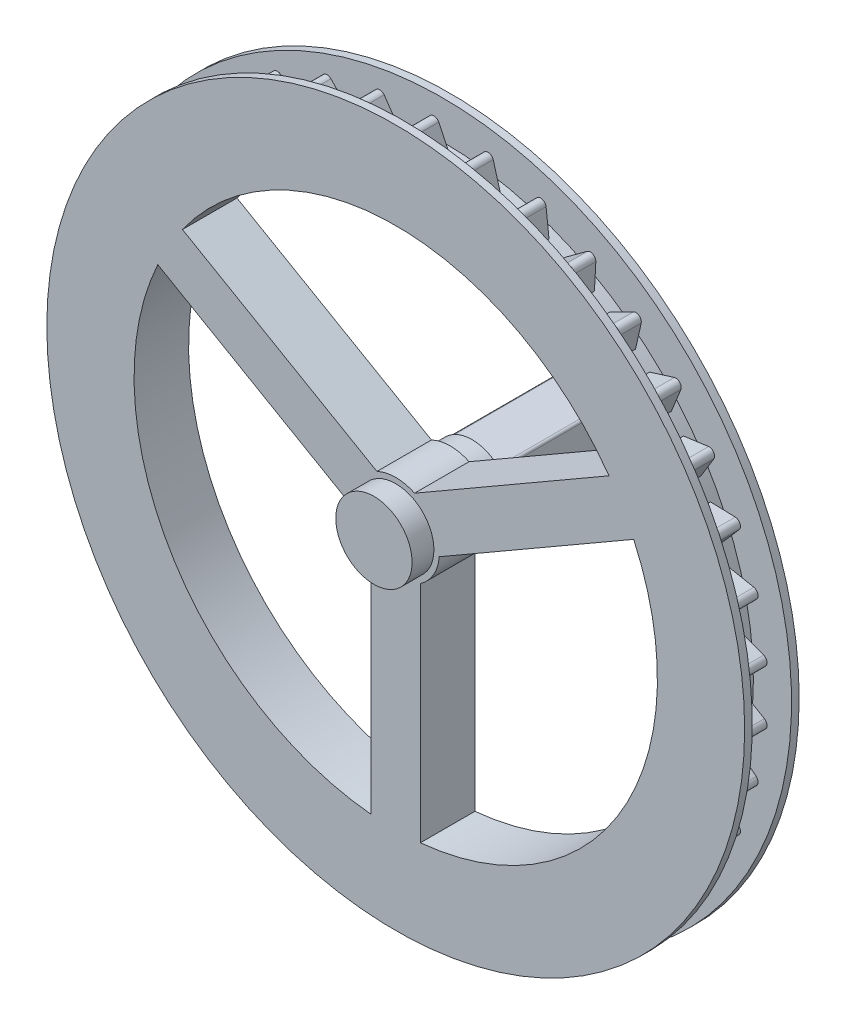
SolidWorks part; units mm, degrees
ref_plane "Front" through (0, 0, 0) normal (0, 0, 1) x (1, 0, 0)
ref_plane "Top" through (0, 0, 0) normal (0, 1, 0) x (1, 0, 0)
ref_plane "Right" through (0, 0, 0) normal (1, 0, 0) x (0, 0, -1)
sketch "Sketch1" plane through (0, 0, 0) normal (0, 0, 1) x (1, 0, 0)
  circle A0 centre (0, 0) radius 40
  dimension "D1" = 80
extrude "Boss-Extrude1" add sketch "Sketch1" along normal blind 5
sketch "Sketch2" plane through (0, 0, 5) normal (0, 0, 1) x (1, 0, 0)
  line L0 (0, 0) -> (0, 40) construction
  line L2 (-2.1584, 4.5101) -> (-24.4518, 17.3813)
  line L4 (2.1584, 4.5101) -> (24.4518, 17.3813)
  line L5 (4.9851, -0.3858) -> (27.2785, 12.4853)
  line L6 (2.8267, -4.1243) -> (2.8267, -29.8665)
  line L7 (0, 0) -> (34.641, -20) construction
  line L8 (-2.8267, -4.1243) -> (-2.8267, -29.8665)
  line L9 (-4.9851, -0.3858) -> (-27.2785, 12.4853)
  line L10 (0, 0) -> (-34.641, -20) construction
  arc A0 (2.1584, 4.5101) -> (-2.1584, 4.5101) centre (0, 0) ccw
  circle A1 centre (0, 0) radius 40 construction
  arc A2 (24.4518, 17.3813) -> (-24.4518, 17.3813) centre (0, 0) ccw
  arc A3 (2.8267, -4.1243) -> (4.9851, -0.3858) centre (0, 0) ccw
  arc A4 (2.8267, -29.8665) -> (27.2785, 12.4853) centre (0, 0) ccw
  arc A5 (-4.9851, -0.3858) -> (-2.8267, -4.1243) centre (0, 0) ccw
  arc A6 (-27.2785, 12.4853) -> (-2.8267, -29.8665) centre (0, 0) ccw
  point P23 (0, 0)
  dimension "D1" = 10
  dimension "D2" = 60
  dimension "D3" = 60
  dimension "D4" = 3
extrude "Cut-Extrude1" cut sketch "Sketch2" against normal blind 5
scale "Scale1" scale about centroid uniform scaling yes scale factor 0.8
sketch "Sketch4" plane through (0, 0, 4.5) normal (0, 0, 1) x (1, 0, 0)
  line L0 (-2.2614, -23.8932) -> (-2.2614, -3.2994) construction
  line L1 (2.2614, -3.2994) -> (2.2614, -23.8932) construction
  line L2 (21.8228, 9.9882) -> (3.9881, -0.3087) construction
  line L3 (-19.5615, 13.905) -> (-1.7267, 3.6081) construction
  line L4 (1.7267, 3.6081) -> (19.5615, 13.905) construction
  line L5 (-2.2614, -23.8932) -> (-2.2614, -3.2994)
  line L6 (2.2614, -3.2994) -> (2.2614, -23.8932)
  line L7 (21.8228, 9.9882) -> (3.9881, -0.3087)
  line L8 (-19.5615, 13.905) -> (-1.7267, 3.6081)
  line L9 (1.7267, 3.6081) -> (19.5615, 13.905)
  circle A0 centre (0, 0) radius 32 construction
  arc A1 (2.2614, -23.8932) -> (21.8228, 9.9882) centre (0, 0) ccw construction
  arc A2 (-21.8228, 9.9882) -> (-2.2614, -23.8932) centre (0, 0) ccw construction
  arc A3 (2.2614, -3.2994) -> (3.9881, -0.3087) centre (0, 0) ccw construction
  arc A4 (1.7267, 3.6081) -> (-1.7267, 3.6081) centre (0, 0) ccw construction
  arc A5 (19.5615, 13.905) -> (-19.5615, 13.905) centre (0, 0) ccw construction
  circle A6 centre (0, 0) radius 32
  arc A7 (2.2614, -23.8932) -> (21.8228, 9.9882) centre (0, 0) ccw
  arc A8 (-21.8228, 9.9882) -> (-2.2614, -23.8932) centre (0, 0) ccw
  arc A9 (2.2614, -3.2994) -> (3.9881, -0.3087) centre (0, 0) ccw
  arc A10 (1.7267, 3.6081) -> (-1.7267, 3.6081) centre (0, 0) ccw
  arc A11 (19.5615, 13.905) -> (-19.5615, 13.905) centre (0, 0) ccw
  arc M1 (-3.9881, -0.3087) -> (-2.2614, -3.2994) centre (0, 0) ccw
  line M2 (-2.2614, -3.2994) -> (-2.2614, -23.8932)
  arc M3 (-2.2614, -23.8932) -> (-21.8228, 9.9882) centre (0, 0) cw
  line M4 (-21.8228, 9.9882) -> (-3.9881, -0.3087)
  arc M5 (2.2614, -3.2994) -> (3.9881, -0.3087) centre (0, 0) ccw
  line M6 (3.9881, -0.3087) -> (21.8228, 9.9882)
  arc M7 (21.8228, 9.9882) -> (2.2614, -23.8932) centre (0, 0) cw
  line M8 (2.2614, -23.8932) -> (2.2614, -3.2994)
  arc M10 (1.7267, 3.6081) -> (-1.7267, 3.6081) centre (0, 0) ccw
  line M11 (-1.7267, 3.6081) -> (-19.5615, 13.905)
  arc M12 (-19.5615, 13.905) -> (19.5615, 13.905) centre (0, 0) cw
  line M13 (19.5615, 13.905) -> (1.7267, 3.6081)
  circle M14 centre (0, 0) radius 32
extrude "Boss-Extrude2" add sketch "Sketch4" along normal blind 1 contours M14 M13 M10 M11 M12 M8 M5 M6 M7 M4 M1 M2 M3 region at (0, 0, 4.5)
sketch "Sketch7" plane through (0, 0, 0.5) normal (0, 0, -1) x (-1, 0, 0)
  circle A0 centre (0, 0) radius 3.5
  dimension "D1" = 7
extrude "Boss-Extrude3" add sketch "Sketch7" along normal blind 2
ref_plane "Plane1" through (0, 0, 0) normal (0, 0, 1) x (1, 0, 0)
ref_plane "Plane2" through (0, 0, 3) normal (0, 0, 1) x (1, 0, 0)
mirror "Mirror1" about plane through (0, 0, 3) normal (0, 0, 1) of "Boss-Extrude3"
sketch "Sketch9" plane through (0, 0, -1.5) normal (0, 0, -1) x (-1, 0, 0)
  line L0 (0, 0) -> (0, -11.4926) construction
  line L1 (-2.2614, -3.2994) -> (-2.2614, -23.8932) construction
  line L2 (0, 0) -> (-15.6668, 0) construction
  line L3 (2.45, -2.45) -> (-2.45, -2.45)
  line L4 (2.45, -2.45) -> (2.45, 2.45)
  line L5 (2.45, 2.45) -> (-2.45, 2.45)
  line L6 (-2.45, -2.45) -> (-2.45, 2.45)
  point P10 (0, -2.45)
  point P11 (-2.45, 0)
  dimension "D1" = 4.9
extrude "Boss-Extrude4" add sketch "Sketch9" along normal blind 10
fillet "Fillet1" radius 0.2 8 edges at (-2.45, 0, -11.5) (0, 2.45, -11.5) (2.45, 0, -11.5) (0, -2.45, -11.5) (2.45, -2.45, -6.5) (-2.45, -2.45, -6.5) (2.45, 2.45, -6.5) (-2.45, 2.45, -6.5)
ref_plane "Plane3" through (0, 0, 0.5) normal (0, 0, -1) x (-1, 0, 0)
ref_plane "Plane4" through (0, 0, 3) normal (0, 0, -1) x (-1, 0, 0)
sketch "Sketch10" plane through (0, 0, 3) normal (0, 0, -1) x (-1, 0, 0)
  circle A0 centre (0, 0) radius 32 construction
  circle A1 centre (0, 0) radius 32
  circle A2 centre (0, 0) radius 28.5
  dimension "D1" = 57
extrude "Cut-Extrude2" cut sketch "Sketch10" against normal blind 1.8 and the other way blind 1.8
sketch "Sketch11" plane through (0, 0, 3) normal (0, 0, -1) x (-1, 0, 0)
  line L0 (0, 0) -> (0, 28.5) construction
  line L2 (0, 28.5) -> (0, 33.0418) construction
  circle A0 centre (0, 0) radius 28.5 construction
  arc A1 (2.8558, 28.3566) -> (-2.8558, 28.3566) centre (0, 0) ccw
  arc A2 (8.5055, 27.2012) -> (2.9108, 28.351) centre (0, 0) ccw
  arc A3 (13.8069, 24.9323) -> (8.5582, 27.1847) centre (0, 0) ccw
  arc A4 (18.5431, 21.6426) -> (13.8553, 24.9055) centre (0, 0) ccw
  arc A5 (22.5202, 17.4669) -> (18.5851, 21.6066) centre (0, 0) ccw
  arc A6 (25.5753, 12.576) -> (22.554, 17.4232) centre (0, 0) ccw
  arc A7 (27.5833, 7.1703) -> (25.5996, 12.5264) centre (0, 0) ccw
  arc A8 (28.462, 1.4711) -> (27.5971, 7.1169) centre (0, 0) ccw
  arc A9 (28.1755, -4.2884) -> (28.4648, 1.4159) centre (0, 0) ccw
  arc A10 (26.7355, -9.8723) -> (28.1672, -4.343) centre (0, 0) ccw
  arc A11 (24.201, -15.052) -> (26.7163, -9.9241) centre (0, 0) ccw
  arc A12 (20.6756, -19.6155) -> (24.1717, -15.0989) centre (0, 0) ccw
  arc A13 (16.3038, -23.376) -> (20.6376, -19.6556) centre (0, 0) ccw
  arc A14 (11.2645, -26.1794) -> (16.2585, -23.4075) centre (0, 0) ccw
  arc A15 (5.7641, -27.911) -> (11.2138, -26.2012) centre (0, 0) ccw
  arc A16 (0.0276, -28.5) -> (5.7099, -27.9222) centre (0, 0) ccw
  arc A17 (-5.7099, -27.9222) -> (-0.0276, -28.5) centre (0, 0) ccw
  arc A18 (-11.2138, -26.2012) -> (-5.7641, -27.911) centre (0, 0) ccw
  arc A19 (-16.2585, -23.4075) -> (-11.2645, -26.1794) centre (0, 0) ccw
  arc A20 (-20.6376, -19.6556) -> (-16.3038, -23.376) centre (0, 0) ccw
  arc A21 (-24.1717, -15.0989) -> (-20.6756, -19.6155) centre (0, 0) ccw
  arc A22 (-26.7163, -9.9241) -> (-24.201, -15.052) centre (0, 0) ccw
  arc A23 (-28.1672, -4.343) -> (-26.7355, -9.8723) centre (0, 0) ccw
  arc A24 (-28.4648, 1.4159) -> (-28.1755, -4.2884) centre (0, 0) ccw
  arc A25 (-27.5971, 7.1169) -> (-28.462, 1.4711) centre (0, 0) ccw
  arc A26 (-25.5996, 12.5264) -> (-27.5833, 7.1703) centre (0, 0) ccw
  arc A27 (-22.554, 17.4232) -> (-25.5753, 12.576) centre (0, 0) ccw
  arc A28 (-18.5851, 21.6066) -> (-22.5202, 17.4669) centre (0, 0) ccw
  arc A29 (-13.8553, 24.9055) -> (-18.5431, 21.6426) centre (0, 0) ccw
  arc A30 (-8.5582, 27.1847) -> (-13.8069, 24.9323) centre (0, 0) ccw
  arc A31 (-2.9108, 28.351) -> (-8.5055, 27.2012) centre (0, 0) ccw
  spline S0 degree 2 poles (-2.8558, 28.3566) (-0.348, 29.1272) (-0.3414, 31.6043) knots 0 0 0 1 1 1
  spline S1 degree 2 poles (2.8558, 28.3566) (0.348, 29.1272) (0.3414, 31.6043) knots 0 0 0 1 1 1
  spline S2 degree 2 poles (-0.3414, 31.6043) (-0.179, 31.6828) (0, 31.6883) knots 0 0 0 1 1 1
  spline S3 degree 2 poles (0.3414, 31.6043) (0.179, 31.6828) (0, 31.6883) knots 0 0 0 1 1 1
  spline S4 degree 2 poles (2.9108, 28.351) (5.5224, 28.601) (6.0275, 31.0261) knots 0 0 0 1 1 1
  spline S5 degree 2 poles (6.0275, 31.0261) (6.2024, 31.0703) (6.3788, 31.0396) knots 0 0 0 1 1 1
  spline S6 degree 2 poles (6.6963, 30.8886) (6.553, 30.9982) (6.3788, 31.0396) knots 0 0 0 1 1 1
  spline S7 degree 2 poles (8.5055, 27.2012) (6.2041, 28.4609) (6.6963, 30.8886) knots 0 0 0 1 1 1
  spline S8 degree 2 poles (8.5582, 27.1847) (11.1667, 26.9039) (12.1496, 29.1776) knots 0 0 0 1 1 1
  spline S9 degree 2 poles (12.1496, 29.1776) (12.3298, 29.1857) (12.4965, 29.1202) knots 0 0 0 1 1 1
  spline S10 degree 2 poles (12.7771, 28.9084) (12.6588, 29.0446) (12.4965, 29.1202) knots 0 0 0 1 1 1
  spline S11 degree 2 poles (13.8069, 24.9323) (11.8062, 26.6294) (12.7771, 28.9084) knots 0 0 0 1 1 1
  spline S12 degree 2 poles (13.8553, 24.9055) (16.3538, 24.1053) (17.7743, 26.1347) knots 0 0 0 1 1 1
  spline S13 degree 2 poles (17.7743, 26.1347) (17.9525, 26.1063) (18.1025, 26.0086) knots 0 0 0 1 1 1
  spline S14 degree 2 poles (18.3347, 25.7446) (18.2463, 25.9018) (18.1025, 26.0086) knots 0 0 0 1 1 1
  spline S15 degree 2 poles (18.5431, 21.6426) (16.925, 23.7077) (18.3347, 25.7446) knots 0 0 0 1 1 1
  spline S16 degree 2 poles (18.5851, 21.6066) (20.8714, 20.3199) (22.6713, 22.0217) knots 0 0 0 1 1 1
  spline S17 degree 2 poles (22.6713, 22.0217) (22.8401, 21.9581) (22.9675, 21.8322) knots 0 0 0 1 1 1
  spline S18 degree 2 poles (23.1418, 21.5269) (23.0868, 21.6987) (22.9675, 21.8322) knots 0 0 0 1 1 1
  spline S19 degree 2 poles (22.5202, 17.4669) (21.3509, 19.8154) (23.1418, 21.5269) knots 0 0 0 1 1 1
  spline S20 degree 2 poles (22.554, 17.4232) (24.5345, 15.7025) (26.6402, 17.0073) knots 0 0 0 1 1 1
  spline S21 degree 2 poles (26.6402, 17.0073) (26.7927, 16.9109) (26.8921, 16.762) knots 0 0 0 1 1 1
  spline S22 degree 2 poles (27.0014, 16.4278) (26.9821, 16.6072) (26.8921, 16.762) knots 0 0 0 1 1 1
  spline S23 degree 2 poles (25.5753, 12.576) (24.9027, 15.1119) (27.0014, 16.4278) knots 0 0 0 1 1 1
  spline S24 degree 2 poles (25.5996, 12.5264) (27.1932, 10.4423) (29.5184, 11.2965) knots 0 0 0 1 1 1
  spline S25 degree 2 poles (29.5184, 11.2965) (29.6484, 11.1714) (29.7158, 11.0055) knots 0 0 0 1 1 1
  spline S26 degree 2 poles (29.7555, 10.6562) (29.7728, 10.8358) (29.7158, 11.0055) knots 0 0 0 1 1 1
  spline S27 degree 2 poles (27.5833, 7.1703) (27.4349, 9.7897) (29.7555, 10.6562) knots 0 0 0 1 1 1
  spline S28 degree 2 poles (27.5971, 7.1169) (28.7386, 4.7546) (31.1881, 5.1232) knots 0 0 0 1 1 1
  spline S29 degree 2 poles (31.1881, 5.1232) (31.2903, 4.9746) (31.3229, 4.7985) knots 0 0 0 1 1 1
  spline S30 degree 2 poles (31.2915, 4.4483) (31.3445, 4.6207) (31.3229, 4.7985) knots 0 0 0 1 1 1
  spline S31 degree 2 poles (28.462, 1.4711) (28.844, 4.0667) (31.2915, 4.4483) knots 0 0 0 1 1 1
  spline S32 degree 2 poles (28.4648, 1.4159) (29.1074, -1.1277) (31.581, -1.2598) knots 0 0 0 1 1 1
  spline S33 degree 2 poles (31.581, -1.2598) (31.6512, -1.426) (31.6476, -1.605) knots 0 0 0 1 1 1
  spline S34 degree 2 poles (31.5464, -1.9417) (31.633, -1.7835) (31.6476, -1.605) knots 0 0 0 1 1 1
  spline S35 degree 2 poles (28.1755, -4.2884) (29.0722, -1.8228) (31.5464, -1.9417) knots 0 0 0 1 1 1
  spline S36 degree 2 poles (28.1672, -4.343) (28.2846, -6.9639) (30.6809, -7.5912) knots 0 0 0 1 1 1
  spline S37 degree 2 poles (30.6809, -7.5912) (30.7162, -7.7681) (30.6767, -7.9428) knots 0 0 0 1 1 1
  spline S38 degree 2 poles (30.5098, -8.2522) (30.6265, -8.1146) (30.6767, -7.9428) knots 0 0 0 1 1 1
  spline S39 degree 2 poles (26.7355, -9.8723) (28.1101, -7.6377) (30.5098, -8.2522) knots 0 0 0 1 1 1
  spline S40 degree 2 poles (26.7163, -9.9241) (26.3038, -12.515) (28.5248, -13.6118) knots 0 0 0 1 1 1
  spline S41 degree 2 poles (28.5248, -13.6118) (28.5238, -13.7922) (28.4499, -13.9553) knots 0 0 0 1 1 1
  spline S42 degree 2 poles (28.2241, -14.2248) (28.3661, -14.1136) (28.4499, -13.9553) knots 0 0 0 1 1 1
  spline S43 degree 2 poles (24.201, -15.052) (25.9973, -13.1399) (28.2241, -14.2248) knots 0 0 0 1 1 1
  spline S44 degree 2 poles (24.1717, -15.0989) (23.2461, -17.5537) (25.2009, -19.0752) knots 0 0 0 1 1 1
  spline S45 degree 2 poles (25.2009, -19.0752) (25.1635, -19.2517) (25.0583, -19.3966) knots 0 0 0 1 1 1
  spline S46 degree 2 poles (24.7829, -19.6151) (24.9444, -19.5348) (25.0583, -19.3966) knots 0 0 0 1 1 1
  spline S47 degree 2 poles (20.6756, -19.6155) (22.8201, -18.1041) (24.7829, -19.6151) knots 0 0 0 1 1 1
  spline S48 degree 2 poles (20.6376, -19.6556) (19.2367, -21.8738) (20.8452, -23.7576) knots 0 0 0 1 1 1
  spline S49 degree 2 poles (20.8452, -23.7576) (20.7731, -23.923) (20.6409, -24.0438) knots 0 0 0 1 1 1
  spline S50 degree 2 poles (20.3271, -24.2024) (20.5015, -24.1561) (20.6409, -24.0438) knots 0 0 0 1 1 1
  spline S51 degree 2 poles (16.3038, -23.376) (18.7086, -22.3271) (20.3271, -24.2024) knots 0 0 0 1 1 1
  spline S52 degree 2 poles (16.2585, -23.4075) (14.4397, -25.2984) (15.6361, -27.4674) knots 0 0 0 1 1 1
  spline S53 degree 2 poles (15.6361, -27.4674) (15.5322, -27.6149) (15.3784, -27.7066) knots 0 0 0 1 1 1
  spline S54 degree 2 poles (15.0391, -27.7988) (15.2192, -27.7886) (15.3784, -27.7066) knots 0 0 0 1 1 1
  spline S55 degree 2 poles (11.2645, -26.1794) (13.8312, -25.6361) (15.0391, -27.7988) knots 0 0 0 1 1 1
  spline S56 degree 2 poles (11.2138, -26.2012) (9.0516, -27.6872) (9.7869, -30.0527) knots 0 0 0 1 1 1
  spline S57 degree 2 poles (9.7869, -30.0527) (9.6554, -30.1762) (9.4863, -30.2351) knots 0 0 0 1 1 1
  spline S58 degree 2 poles (9.1354, -30.2571) (9.3139, -30.2834) (9.4863, -30.2351) knots 0 0 0 1 1 1
  spline S59 degree 2 poles (5.7641, -27.911) (8.3876, -27.8955) (9.1354, -30.2571) knots 0 0 0 1 1 1
  spline S60 degree 2 poles (5.7099, -27.9222) (3.2929, -28.9425) (3.537, -31.4076) knots 0 0 0 1 1 1
  spline S61 degree 2 poles (3.537, -31.4076) (3.3834, -31.5021) (3.2059, -31.5257) knots 0 0 0 1 1 1
  spline S62 degree 2 poles (2.8577, -31.4767) (3.0272, -31.5383) (3.2059, -31.5257) knots 0 0 0 1 1 1
  spline S63 degree 2 poles (0.0276, -28.5) (2.6006, -29.0129) (2.8577, -31.4767) knots 0 0 0 1 1 1
  spline S64 degree 2 poles (-0.0276, -28.5) (-2.6006, -29.0129) (-2.8577, -31.4767) knots 0 0 0 1 1 1
  spline S65 degree 2 poles (-2.8577, -31.4767) (-3.0272, -31.5383) (-3.2059, -31.5257) knots 0 0 0 1 1 1
  spline S66 degree 2 poles (-3.537, -31.4076) (-3.3834, -31.5021) (-3.2059, -31.5257) knots 0 0 0 1 1 1
  spline S67 degree 2 poles (-5.7099, -27.9222) (-3.2929, -28.9425) (-3.537, -31.4076) knots 0 0 0 1 1 1
  spline S68 degree 2 poles (-5.7641, -27.911) (-8.3876, -27.8955) (-9.1354, -30.2571) knots 0 0 0 1 1 1
  spline S69 degree 2 poles (-9.1354, -30.2571) (-9.3139, -30.2834) (-9.4863, -30.2351) knots 0 0 0 1 1 1
  spline S70 degree 2 poles (-9.7869, -30.0527) (-9.6554, -30.1762) (-9.4863, -30.2351) knots 0 0 0 1 1 1
  spline S71 degree 2 poles (-11.2138, -26.2012) (-9.0516, -27.6872) (-9.7869, -30.0527) knots 0 0 0 1 1 1
  spline S72 degree 2 poles (-11.2645, -26.1794) (-13.8312, -25.6361) (-15.0391, -27.7988) knots 0 0 0 1 1 1
  spline S73 degree 2 poles (-15.0391, -27.7988) (-15.2192, -27.7886) (-15.3784, -27.7066) knots 0 0 0 1 1 1
  spline S74 degree 2 poles (-15.6361, -27.4674) (-15.5322, -27.6149) (-15.3784, -27.7066) knots 0 0 0 1 1 1
  spline S75 degree 2 poles (-16.2585, -23.4075) (-14.4397, -25.2984) (-15.6361, -27.4674) knots 0 0 0 1 1 1
  spline S76 degree 2 poles (-16.3038, -23.376) (-18.7086, -22.3271) (-20.3271, -24.2024) knots 0 0 0 1 1 1
  spline S77 degree 2 poles (-20.3271, -24.2024) (-20.5015, -24.1561) (-20.6409, -24.0438) knots 0 0 0 1 1 1
  spline S78 degree 2 poles (-20.8452, -23.7576) (-20.7731, -23.923) (-20.6409, -24.0438) knots 0 0 0 1 1 1
  spline S79 degree 2 poles (-20.6376, -19.6556) (-19.2367, -21.8738) (-20.8452, -23.7576) knots 0 0 0 1 1 1
  spline S80 degree 2 poles (-20.6756, -19.6155) (-22.8201, -18.1041) (-24.7829, -19.6151) knots 0 0 0 1 1 1
  spline S81 degree 2 poles (-24.7829, -19.6151) (-24.9444, -19.5348) (-25.0583, -19.3966) knots 0 0 0 1 1 1
  spline S82 degree 2 poles (-25.2009, -19.0752) (-25.1635, -19.2517) (-25.0583, -19.3966) knots 0 0 0 1 1 1
  spline S83 degree 2 poles (-24.1717, -15.0989) (-23.2461, -17.5537) (-25.2009, -19.0752) knots 0 0 0 1 1 1
  spline S84 degree 2 poles (-24.201, -15.052) (-25.9973, -13.1399) (-28.2241, -14.2248) knots 0 0 0 1 1 1
  spline S85 degree 2 poles (-28.2241, -14.2248) (-28.3661, -14.1136) (-28.4499, -13.9553) knots 0 0 0 1 1 1
  spline S86 degree 2 poles (-28.5248, -13.6118) (-28.5238, -13.7922) (-28.4499, -13.9553) knots 0 0 0 1 1 1
  spline S87 degree 2 poles (-26.7163, -9.9241) (-26.3038, -12.515) (-28.5248, -13.6118) knots 0 0 0 1 1 1
  spline S88 degree 2 poles (-26.7355, -9.8723) (-28.1101, -7.6377) (-30.5098, -8.2522) knots 0 0 0 1 1 1
  spline S89 degree 2 poles (-30.5098, -8.2522) (-30.6265, -8.1146) (-30.6767, -7.9428) knots 0 0 0 1 1 1
  spline S90 degree 2 poles (-30.6809, -7.5912) (-30.7162, -7.7681) (-30.6767, -7.9428) knots 0 0 0 1 1 1
  spline S91 degree 2 poles (-28.1672, -4.343) (-28.2846, -6.9639) (-30.6809, -7.5912) knots 0 0 0 1 1 1
  spline S92 degree 2 poles (-28.1755, -4.2884) (-29.0722, -1.8228) (-31.5464, -1.9417) knots 0 0 0 1 1 1
  spline S93 degree 2 poles (-31.5464, -1.9417) (-31.633, -1.7835) (-31.6476, -1.605) knots 0 0 0 1 1 1
  spline S94 degree 2 poles (-31.581, -1.2598) (-31.6512, -1.426) (-31.6476, -1.605) knots 0 0 0 1 1 1
  spline S95 degree 2 poles (-28.4648, 1.4159) (-29.1074, -1.1277) (-31.581, -1.2598) knots 0 0 0 1 1 1
  spline S96 degree 2 poles (-28.462, 1.4711) (-28.844, 4.0667) (-31.2915, 4.4483) knots 0 0 0 1 1 1
  spline S97 degree 2 poles (-31.2915, 4.4483) (-31.3445, 4.6207) (-31.3229, 4.7985) knots 0 0 0 1 1 1
  spline S98 degree 2 poles (-31.1881, 5.1232) (-31.2903, 4.9746) (-31.3229, 4.7985) knots 0 0 0 1 1 1
  spline S99 degree 2 poles (-27.5971, 7.1169) (-28.7386, 4.7546) (-31.1881, 5.1232) knots 0 0 0 1 1 1
  spline S100 degree 2 poles (-27.5833, 7.1703) (-27.4349, 9.7897) (-29.7555, 10.6562) knots 0 0 0 1 1 1
  spline S101 degree 2 poles (-29.7555, 10.6562) (-29.7728, 10.8358) (-29.7158, 11.0055) knots 0 0 0 1 1 1
  spline S102 degree 2 poles (-29.5184, 11.2965) (-29.6484, 11.1714) (-29.7158, 11.0055) knots 0 0 0 1 1 1
  spline S103 degree 2 poles (-25.5996, 12.5264) (-27.1932, 10.4423) (-29.5184, 11.2965) knots 0 0 0 1 1 1
  spline S104 degree 2 poles (-25.5753, 12.576) (-24.9027, 15.1119) (-27.0014, 16.4278) knots 0 0 0 1 1 1
  spline S105 degree 2 poles (-27.0014, 16.4278) (-26.9821, 16.6072) (-26.8921, 16.762) knots 0 0 0 1 1 1
  spline S106 degree 2 poles (-26.6402, 17.0073) (-26.7927, 16.9109) (-26.8921, 16.762) knots 0 0 0 1 1 1
  spline S107 degree 2 poles (-22.554, 17.4232) (-24.5345, 15.7025) (-26.6402, 17.0073) knots 0 0 0 1 1 1
  spline S108 degree 2 poles (-22.5202, 17.4669) (-21.3509, 19.8154) (-23.1418, 21.5269) knots 0 0 0 1 1 1
  spline S109 degree 2 poles (-23.1418, 21.5269) (-23.0868, 21.6987) (-22.9675, 21.8322) knots 0 0 0 1 1 1
  spline S110 degree 2 poles (-22.6713, 22.0217) (-22.8401, 21.9581) (-22.9675, 21.8322) knots 0 0 0 1 1 1
  spline S111 degree 2 poles (-18.5851, 21.6066) (-20.8714, 20.3199) (-22.6713, 22.0217) knots 0 0 0 1 1 1
  spline S112 degree 2 poles (-18.5431, 21.6426) (-16.925, 23.7077) (-18.3347, 25.7446) knots 0 0 0 1 1 1
  spline S113 degree 2 poles (-18.3347, 25.7446) (-18.2463, 25.9018) (-18.1025, 26.0086) knots 0 0 0 1 1 1
  spline S114 degree 2 poles (-17.7743, 26.1347) (-17.9525, 26.1063) (-18.1025, 26.0086) knots 0 0 0 1 1 1
  spline S115 degree 2 poles (-13.8553, 24.9055) (-16.3538, 24.1053) (-17.7743, 26.1347) knots 0 0 0 1 1 1
  spline S116 degree 2 poles (-13.8069, 24.9323) (-11.8062, 26.6294) (-12.7771, 28.9084) knots 0 0 0 1 1 1
  spline S117 degree 2 poles (-12.7771, 28.9084) (-12.6588, 29.0446) (-12.4965, 29.1202) knots 0 0 0 1 1 1
  spline S118 degree 2 poles (-12.1496, 29.1776) (-12.3298, 29.1857) (-12.4965, 29.1202) knots 0 0 0 1 1 1
  spline S119 degree 2 poles (-8.5582, 27.1847) (-11.1667, 26.9039) (-12.1496, 29.1776) knots 0 0 0 1 1 1
  spline S120 degree 2 poles (-8.5055, 27.2012) (-6.2041, 28.4609) (-6.6963, 30.8886) knots 0 0 0 1 1 1
  spline S121 degree 2 poles (-6.6963, 30.8886) (-6.553, 30.9982) (-6.3788, 31.0396) knots 0 0 0 1 1 1
  spline S122 degree 2 poles (-6.0275, 31.0261) (-6.2024, 31.0703) (-6.3788, 31.0396) knots 0 0 0 1 1 1
  spline S123 degree 2 poles (-2.9108, 28.351) (-5.5224, 28.601) (-6.0275, 31.0261) knots 0 0 0 1 1 1
  point P286 (0, 0)
  dimension "D1" = 31
extrude "Boss-Extrude5" add sketch "Sketch11" along normal blind 1 and the other way blind 1
sketch "Sketch13" plane through (0, 0, 3) normal (0, 0, -1) x (-1, 0, 0)
  arc A0 (-27.5971, 7.1169) -> (-28.462, 1.4711) centre (0, 0) ccw construction
  circle A1 centre (0, 0) radius 28.5
  circle A2 centre (0, 0) radius 32
  circle A3 centre (0, 0) radius 32 construction
extrude "Cut-Extrude3" cut sketch "Sketch13" against normal blind 1 and the other way blind 1
sketch "Sketch14" plane through (0, 0, 3) normal (0, 0, -1) x (-1, 0, 0)
  line L0 (0, 0) -> (0, 28.4605) construction
  line L3 (-1.5, 28.4605) -> (1.5, 28.4605)
  line L4 (0.4437, 30.6911) -> (1.5, 28.4605)
  line L5 (0, 28.4605) -> (0, 30.9605) construction
  line L6 (-0.4437, 30.6911) -> (-1.5, 28.4605)
  line L7 (3.1543, 28.3234) -> (6.1134, 27.8296)
  line L8 (5.4386, 30.2037) -> (6.1134, 27.8296)
  line L9 (4.5634, 30.3497) -> (3.1543, 28.3234)
  line L10 (7.7226, 27.4221) -> (10.5601, 26.448)
  line L11 (10.2852, 28.9007) -> (10.5601, 26.448)
  line L12 (9.446, 29.1889) -> (7.7226, 27.4221)
  line L13 (12.0803, 25.7812) -> (14.7187, 24.3534)
  line L14 (14.8513, 26.8179) -> (14.7187, 24.3534)
  line L15 (14.0709, 27.2402) -> (12.0803, 25.7812)
  line L16 (16.1084, 23.4454) -> (18.4758, 21.6028)
  line L17 (19.0122, 24.0119) -> (18.4758, 21.6028)
  line L18 (18.312, 24.5569) -> (16.1084, 23.4454)
  line L19 (19.6971, 20.4785) -> (21.7289, 18.2713)
  line L20 (22.6546, 20.5592) -> (21.7289, 18.2713)
  line L21 (22.0536, 21.2121) -> (19.6971, 20.4785)
  line L22 (22.7485, 16.9614) -> (24.3894, 14.4499)
  line L23 (25.679, 16.5542) -> (24.3894, 14.4499)
  line L24 (25.1937, 17.297) -> (22.7485, 16.9614)
  line L25 (25.1794, 12.9899) -> (26.3845, 10.2426)
  line L26 (28.0029, 12.106) -> (26.3845, 10.2426)
  line L27 (27.6465, 12.9186) -> (25.1794, 12.9899)
  line L28 (26.9235, 8.6726) -> (27.66, 5.7644)
  line L29 (29.563, 7.336) -> (27.66, 5.7644)
  line L30 (29.3452, 8.1961) -> (26.9235, 8.6726)
  line L31 (27.9332, 4.127) -> (28.181, 1.1373)
  line L32 (30.3167, 2.3742) -> (28.181, 1.1373)
  line L33 (30.2434, 3.2585) -> (27.9332, 4.127)
  line L34 (28.181, -0.5227) -> (27.9332, -3.5125)
  line L35 (30.2434, -2.644) -> (27.9332, -3.5125)
  line L36 (30.3167, -1.7597) -> (28.181, -0.5227)
  line L37 (27.66, -5.1499) -> (26.9235, -8.0581)
  line L38 (29.3452, -7.5816) -> (26.9235, -8.0581)
  line L39 (29.563, -6.7214) -> (27.66, -5.1499)
  line L40 (26.3845, -9.6281) -> (25.1794, -12.3754)
  line L41 (27.6465, -12.3041) -> (25.1794, -12.3754)
  line L42 (28.0029, -11.4915) -> (26.3845, -9.6281)
  line L43 (24.3894, -13.8354) -> (22.7485, -16.3469)
  line L44 (25.1937, -16.6825) -> (22.7485, -16.3469)
  line L45 (25.679, -15.9397) -> (24.3894, -13.8354)
  line L46 (21.7289, -17.6568) -> (19.6971, -19.864)
  line L47 (22.0536, -20.5976) -> (19.6971, -19.864)
  line L48 (22.6546, -19.9447) -> (21.7289, -17.6568)
  line L49 (18.4758, -20.9883) -> (16.1084, -22.8309)
  line L50 (18.312, -23.9424) -> (16.1084, -22.8309)
  line L51 (19.0122, -23.3974) -> (18.4758, -20.9883)
  line L52 (14.7187, -23.7389) -> (12.0803, -25.1667)
  line L53 (14.0709, -26.6257) -> (12.0803, -25.1667)
  line L54 (14.8513, -26.2034) -> (14.7187, -23.7389)
  line L55 (10.5601, -25.8335) -> (7.7226, -26.8076)
  line L56 (9.446, -28.5743) -> (7.7226, -26.8076)
  line L57 (10.2852, -28.2862) -> (10.5601, -25.8335)
  line L58 (6.1134, -27.2151) -> (3.1543, -27.7089)
  line L59 (4.5634, -29.7352) -> (3.1543, -27.7089)
  line L60 (5.4386, -29.5891) -> (6.1134, -27.2151)
  line L61 (1.5, -27.846) -> (-1.5, -27.846)
  line L62 (-0.4437, -30.0766) -> (-1.5, -27.846)
  line L63 (0.4437, -30.0766) -> (1.5, -27.846)
  line L64 (-3.1543, -27.7089) -> (-6.1134, -27.2151)
  line L65 (-5.4386, -29.5891) -> (-6.1134, -27.2151)
  line L66 (-4.5634, -29.7352) -> (-3.1543, -27.7089)
  line L67 (-7.7226, -26.8076) -> (-10.5601, -25.8335)
  line L68 (-10.2852, -28.2862) -> (-10.5601, -25.8335)
  line L69 (-9.446, -28.5743) -> (-7.7226, -26.8076)
  line L70 (-12.0803, -25.1667) -> (-14.7187, -23.7389)
  line L71 (-14.8513, -26.2034) -> (-14.7187, -23.7389)
  line L72 (-14.0709, -26.6257) -> (-12.0803, -25.1667)
  line L73 (-16.1084, -22.8309) -> (-18.4758, -20.9883)
  line L74 (-19.0122, -23.3974) -> (-18.4758, -20.9883)
  line L75 (-18.312, -23.9424) -> (-16.1084, -22.8309)
  line L76 (-19.6971, -19.864) -> (-21.7289, -17.6568)
  line L77 (-22.6546, -19.9447) -> (-21.7289, -17.6568)
  line L78 (-22.0536, -20.5976) -> (-19.6971, -19.864)
  line L79 (-22.7485, -16.3469) -> (-24.3894, -13.8354)
  line L80 (-25.679, -15.9397) -> (-24.3894, -13.8354)
  line L81 (-25.1937, -16.6825) -> (-22.7485, -16.3469)
  line L82 (-25.1794, -12.3754) -> (-26.3845, -9.6281)
  line L83 (-28.0029, -11.4915) -> (-26.3845, -9.6281)
  line L84 (-27.6465, -12.3041) -> (-25.1794, -12.3754)
  line L85 (-26.9235, -8.0581) -> (-27.66, -5.1499)
  line L86 (-29.563, -6.7214) -> (-27.66, -5.1499)
  line L87 (-29.3452, -7.5816) -> (-26.9235, -8.0581)
  line L88 (-27.9332, -3.5125) -> (-28.181, -0.5227)
  line L89 (-30.3167, -1.7597) -> (-28.181, -0.5227)
  line L90 (-30.2434, -2.644) -> (-27.9332, -3.5125)
  line L91 (-28.181, 1.1373) -> (-27.9332, 4.127)
  line L92 (-30.2434, 3.2585) -> (-27.9332, 4.127)
  line L93 (-30.3167, 2.3742) -> (-28.181, 1.1373)
  line L94 (-27.66, 5.7644) -> (-26.9235, 8.6726)
  line L95 (-29.3452, 8.1961) -> (-26.9235, 8.6726)
  line L96 (-29.563, 7.336) -> (-27.66, 5.7644)
  line L97 (-26.3845, 10.2426) -> (-25.1794, 12.9899)
  line L98 (-27.6465, 12.9186) -> (-25.1794, 12.9899)
  line L99 (-28.0029, 12.106) -> (-26.3845, 10.2426)
  line L100 (-24.3894, 14.4499) -> (-22.7485, 16.9614)
  line L101 (-25.1937, 17.297) -> (-22.7485, 16.9614)
  line L102 (-25.679, 16.5542) -> (-24.3894, 14.4499)
  line L103 (-21.7289, 18.2713) -> (-19.6971, 20.4785)
  line L104 (-22.0536, 21.2121) -> (-19.6971, 20.4785)
  line L105 (-22.6546, 20.5592) -> (-21.7289, 18.2713)
  line L106 (-18.4758, 21.6028) -> (-16.1084, 23.4454)
  line L107 (-18.312, 24.5569) -> (-16.1084, 23.4454)
  line L108 (-19.0122, 24.0119) -> (-18.4758, 21.6028)
  line L109 (-14.7187, 24.3534) -> (-12.0803, 25.7812)
  line L110 (-14.0709, 27.2402) -> (-12.0803, 25.7812)
  line L111 (-14.8513, 26.8179) -> (-14.7187, 24.3534)
  line L112 (-10.5601, 26.448) -> (-7.7226, 27.4221)
  line L113 (-9.446, 29.1889) -> (-7.7226, 27.4221)
  line L114 (-10.2852, 28.9007) -> (-10.5601, 26.448)
  line L115 (-6.1134, 27.8296) -> (-3.1543, 28.3234)
  line L116 (-4.5634, 30.3497) -> (-3.1543, 28.3234)
  line L117 (-5.4386, 30.2037) -> (-6.1134, 27.8296)
  arc A1 (0.4437, 30.6911) -> (-0.4437, 30.6911) centre (0, 30.4605) ccw
  arc A5 (5.4386, 30.2037) -> (4.5634, 30.3497) centre (4.9631, 30.0492) ccw
  arc A6 (10.2852, 28.9007) -> (9.446, 29.1889) centre (9.7907, 28.8267) ccw
  arc A7 (14.8513, 26.8179) -> (14.0709, 27.2402) centre (14.3514, 26.8262) ccw
  arc A8 (19.0122, 24.0119) -> (18.312, 24.5569) centre (18.5205, 24.1024) ccw
  arc A9 (22.6546, 20.5592) -> (22.0536, 21.2121) centre (22.1845, 20.7295) ccw
  arc A10 (25.679, 16.5542) -> (25.1937, 17.297) centre (25.2433, 16.7995) ccw
  arc A11 (28.0029, 12.106) -> (27.6465, 12.9186) centre (27.6135, 12.4197) ccw
  arc A12 (29.563, 7.336) -> (29.3452, 8.1961) centre (29.2306, 7.7094) ccw
  arc A13 (30.3167, 2.3742) -> (30.2434, 3.2585) centre (30.0503, 2.7973) ccw
  arc A14 (30.2434, -2.644) -> (30.3167, -1.7597) centre (30.0503, -2.1828) ccw
  arc A15 (29.3452, -7.5816) -> (29.563, -6.7214) centre (29.2306, -7.0949) ccw
  arc A16 (27.6465, -12.3041) -> (28.0029, -11.4915) centre (27.6135, -11.8052) ccw
  arc A17 (25.1937, -16.6825) -> (25.679, -15.9397) centre (25.2433, -16.185) ccw
  arc A18 (22.0536, -20.5976) -> (22.6546, -19.9447) centre (22.1845, -20.115) ccw
  arc A19 (18.312, -23.9424) -> (19.0122, -23.3974) centre (18.5205, -23.4879) ccw
  arc A20 (14.0709, -26.6257) -> (14.8513, -26.2034) centre (14.3514, -26.2117) ccw
  arc A21 (9.446, -28.5743) -> (10.2852, -28.2862) centre (9.7907, -28.2122) ccw
  arc A22 (4.5634, -29.7352) -> (5.4386, -29.5891) centre (4.9631, -29.4347) ccw
  arc A23 (-0.4437, -30.0766) -> (0.4437, -30.0766) centre (0, -29.846) ccw
  arc A24 (-5.4386, -29.5891) -> (-4.5634, -29.7352) centre (-4.9631, -29.4347) ccw
  arc A25 (-10.2852, -28.2862) -> (-9.446, -28.5743) centre (-9.7907, -28.2122) ccw
  arc A26 (-14.8513, -26.2034) -> (-14.0709, -26.6257) centre (-14.3514, -26.2117) ccw
  arc A27 (-19.0122, -23.3974) -> (-18.312, -23.9424) centre (-18.5205, -23.4879) ccw
  arc A28 (-22.6546, -19.9447) -> (-22.0536, -20.5976) centre (-22.1845, -20.115) ccw
  arc A29 (-25.679, -15.9397) -> (-25.1937, -16.6825) centre (-25.2433, -16.185) ccw
  arc A30 (-28.0029, -11.4915) -> (-27.6465, -12.3041) centre (-27.6135, -11.8052) ccw
  arc A31 (-29.563, -6.7214) -> (-29.3452, -7.5816) centre (-29.2306, -7.0949) ccw
  arc A32 (-30.3167, -1.7597) -> (-30.2434, -2.644) centre (-30.0503, -2.1828) ccw
  arc A33 (-30.2434, 3.2585) -> (-30.3167, 2.3742) centre (-30.0503, 2.7973) ccw
  arc A34 (-29.3452, 8.1961) -> (-29.563, 7.336) centre (-29.2306, 7.7094) ccw
  arc A35 (-27.6465, 12.9186) -> (-28.0029, 12.106) centre (-27.6135, 12.4197) ccw
  arc A36 (-25.1937, 17.297) -> (-25.679, 16.5542) centre (-25.2433, 16.7995) ccw
  arc A37 (-22.0536, 21.2121) -> (-22.6546, 20.5592) centre (-22.1845, 20.7295) ccw
  arc A38 (-18.312, 24.5569) -> (-19.0122, 24.0119) centre (-18.5205, 24.1024) ccw
  arc A39 (-14.0709, 27.2402) -> (-14.8513, 26.8179) centre (-14.3514, 26.8262) ccw
  arc A40 (-9.446, 29.1889) -> (-10.2852, 28.9007) centre (-9.7907, 28.8267) ccw
  arc A41 (-4.5634, 30.3497) -> (-5.4386, 30.2037) centre (-4.9631, 30.0492) ccw
  point P169 (0, 0.3073)
  point P198 (0, 0)
  dimension "D2" = 0.5
  dimension "D1" = 2.5
  dimension "D3" = 3
  dimension "D4" = 0.8873
  dimension "D6" = 1.66
  dimension "D5" = 38
extrude "Boss-Extrude6" add sketch "Sketch14" along normal blind 1 and the other way blind 1
ref_plane "Plane5" through (0, 0, 3) normal (0, 0, 1) x (1, 0, 0)
